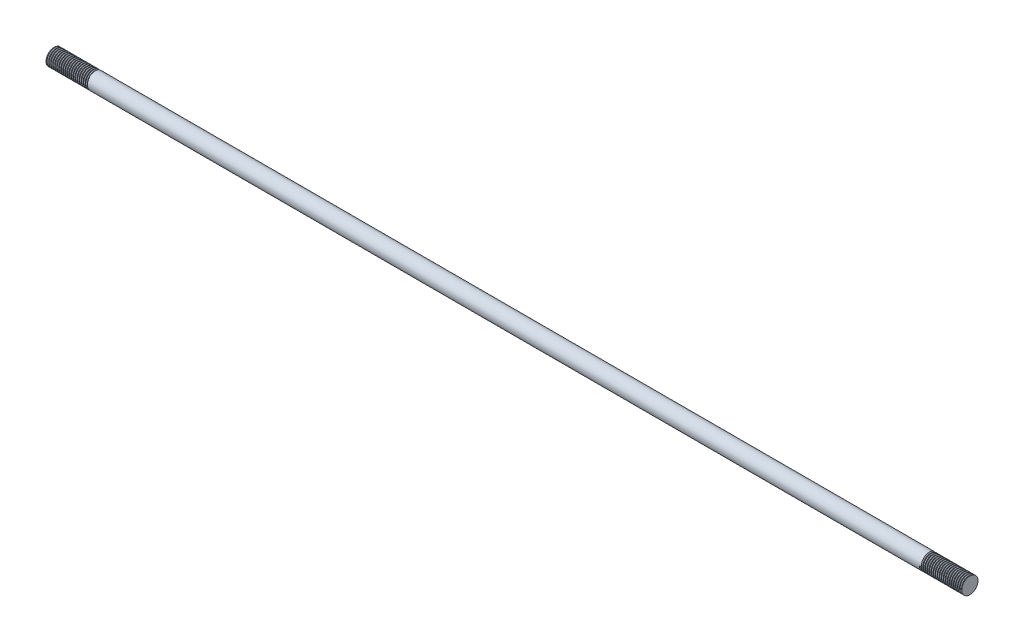
SolidWorks part; units mm, degrees
ref_plane "Front Plane" through (0, 0, 0) normal (0, 0, 1) x (1, 0, 0)
ref_plane "Top Plane" through (0, 0, 0) normal (0, 1, 0) x (1, 0, 0)
ref_plane "Right Plane" through (0, 0, 0) normal (1, 0, 0) x (0, 0, -1)
sketch "Sketch1" plane through (0, 0, 0) normal (1, 0, 0) x (0, 0, -1)
  circle A0 centre (0, 0) radius 8
  dimension "D1" = 16
extrude "Boss-Extrude1" add sketch "Sketch1" along normal mid plane 900
thread "Thread1" pitch 2 method cut profile "Thread Profile1" start angle 0, offset 0, length 40, pitch 2, diameter 16
ref_plane "Plane1" through (450, 0, 8) normal (0, -1, 0) x (0, 0, 1)
sketch "Thread Profile1" plane through (450, 0, 8) normal (0, -1, 0) x (0, 0, 1)
  line L0 (0, 0) -> (0, 2) construction
  line L11 (0, 0) -> (0, 1.75)
  line L12 (0, 1.75) -> (-1.0825, 1.125)
  line L13 (-1.0825, 1.125) -> (-1.0825, 0.625)
  line L15 (-1.0825, 0.625) -> (0, 0)
  line L17 (-1.0825, 0.875) -> (0, 0.875) construction
  point P2 (0, 0)
  dimension "Pitch" = 2
  dimension "Profile_Angle" = 60
  dimension "Profile_Land" = 0.5
  dimension "Profile_Height" = 1.0825
thread "Thread2" pitch 2 method cut profile "Thread Profile2" start angle 0, offset 0, length 40, pitch 2, diameter 16
ref_plane "Plane2" through (-450, 0, -8) normal (0, -1, 0) x (0, 0, -1)
sketch "Thread Profile2" plane through (-450, 0, -8) normal (0, -1, 0) x (0, 0, -1)
  line L0 (0, 0) -> (0, 2) construction
  line L11 (0, 0) -> (0, 1.75)
  line L12 (0, 1.75) -> (-1.0825, 1.125)
  line L13 (-1.0825, 1.125) -> (-1.0825, 0.625)
  line L15 (-1.0825, 0.625) -> (0, 0)
  line L17 (-1.0825, 0.875) -> (0, 0.875) construction
  point P2 (0, 0)
  dimension "Pitch" = 2
  dimension "Profile_Angle" = 60
  dimension "Profile_Land" = 0.5
  dimension "Profile_Height" = 1.0825
